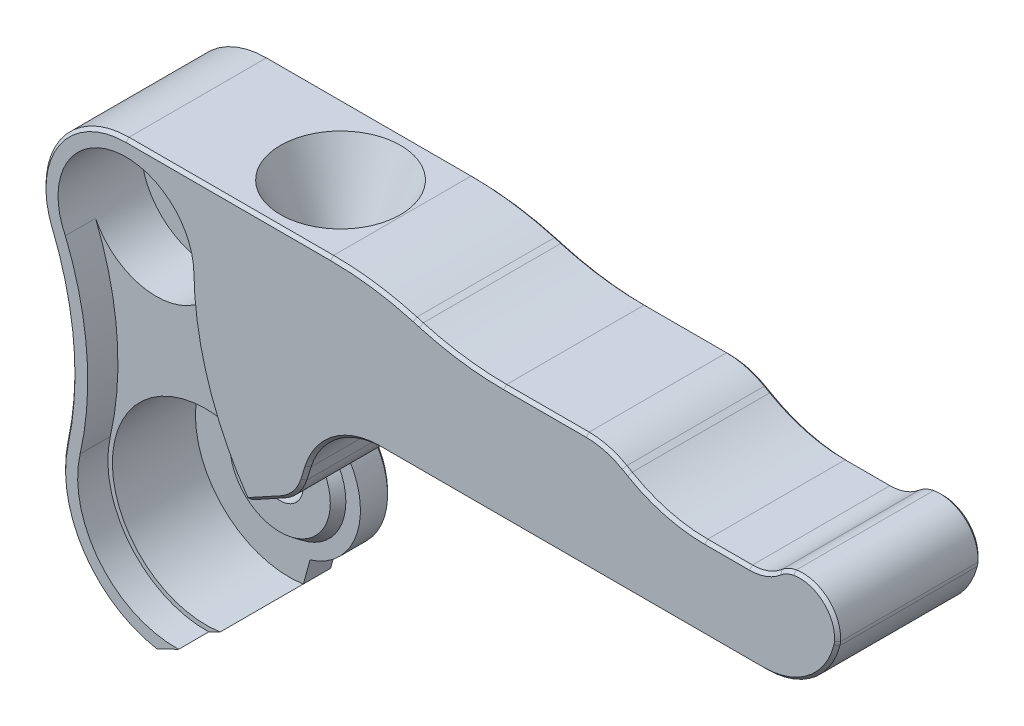
SolidWorks part; units mm, degrees
ref_plane "前视基准面" through (0, 0, 0) normal (0, 0, 1) x (1, 0, 0)
ref_plane "上视基准面" through (0, 0, 0) normal (0, 1, 0) x (1, 0, 0)
ref_plane "右视基准面" through (0, 0, 0) normal (1, 0, 0) x (0, 0, -1)
ref_plane "基准面4" through (0, 0, 14.66) normal (0, 0, 1) x (1, 0, 0)
sketch "草图1" plane through (0, 0, 14.66) normal (0, 0, 1) x (1, 0, 0)
  line L0 (10.0139, 11.6407) -> (26.6958, 11.6407)
  line L2 (-13.7752, -7.3412) -> (-11.2882, -6.1227)
  line L3 (-11.2882, -6.1227) -> (-10.8536, -4.519)
  line L4 (0, 0) -> (50000, 0) construction
  line L5 (-15.5381, 21.0307) -> (-1.986, 21.0307)
  line L6 (-8.9914, 3.4337) -> (-5.1856, 5.5218)
  line L7 (0, 0) -> (0, 50000) construction
  line L8 (-37.0818, 21.1307) -> (32.8827, 21.1307) construction
  line L9 (-21.0381, 33.3889) -> (-21.0381, -18.7776) construction
  line L10 (3.5318, 20.2545) -> (3.954, 20.1333)
  line L12 (9.4717, 19.3571) -> (14.9362, 19.3571)
  line L13 (17.436, 18.6873) -> (17.7909, 18.4824)
  line L14 (22.7906, 17.1429) -> (25.7538, 17.1429)
  line L17 (-3.7672, 7.2509) -> (-3.4865, 8.1424)
  line L18 (1.2827, 11.6407) -> (10.0139, 11.6407)
  arc A0 (-10.8536, -4.519) -> (-8.9914, 3.4337) centre (-12.24, 0) ccw
  arc A1 (-1.986, 21.0307) -> (3.5318, 20.2545) centre (-1.986, 1.0307) cw
  arc A2 (3.954, 20.1333) -> (9.4717, 19.3571) centre (9.4717, 39.3571) ccw
  arc A3 (17.7909, 18.4824) -> (22.7906, 17.1429) centre (22.7906, 27.1429) ccw
  arc A4 (-15.5381, 21.0307) -> (-20.6238, 13.4363) centre (-15.5381, 15.5307) ccw
  arc A5 (-20.6238, 13.4363) -> (-19.5701, 1.5874) centre (-39.117, 5.8205) cw
  arc A6 (-19.5701, 1.5874) -> (-13.7752, -7.3412) centre (-12.24, 0) ccw
  arc A7 (-3.4865, 8.1424) -> (1.2827, 11.6407) centre (1.2827, 6.6407) cw
  arc A8 (26.6958, 11.6407) -> (31.5407, 15.4052) centre (26.6958, 16.6407) ccw
  arc A9 (14.9362, 19.3571) -> (17.436, 18.6873) centre (14.9362, 14.3571) cw
  arc A10 (-5.1856, 5.5218) -> (-3.7672, 7.2509) centre (-6.6287, 8.1519) ccw
  arc A11 (25.7538, 17.1429) -> (27.7036, 17.8629) centre (25.7538, 20.1429) ccw
  arc A12 (28.6527, 18.3119) -> (31.5829, 15.6621) centre (29.091, 15.8516) cw
  arc A13 (28.6527, 18.3119) -> (27.7036, 17.8629) centre (29.0035, 16.3429) ccw
  arc A14 (31.5829, 15.6621) -> (31.5407, 15.4052) centre (30.0872, 15.7758) cw
  dimension "D2" = 20
  dimension "D6" = 5.5
  dimension "D9" = 4.7269
  dimension "D10" = 7.5
  dimension "D11" = 20
  dimension "D12" = 20
  dimension "D13" = 5
  dimension "D14" = 10
  dimension "D15" = 5
  dimension "D16" = 5
  dimension "D17" = 3
  dimension "D18" = 3
  dimension "D19" = 2
  dimension "D20" = 1.5
  dimension "D3" = 12.24
  dimension "D4" = 15.5381
  dimension "D5" = 15.5307
  dimension "D7" = 5.5
  dimension "D8" = 5.6
extrude "凸台-拉伸1" add sketch "草图1" against normal blind 9.5
sketch "草图2" plane through (0, 0, 14.66) normal (0, 0, 1) x (1, 0, 0)
  line L5 (-1.5033, 0) -> (49998.4967, 0) construction
  line L6 (0, -0.31) -> (0, 49999.69) construction
  arc A0 (-18.5763, 1.4497) -> (-7.0407, 3.9009) centre (-12.24, 0) ccw
  arc A1 (-7.0407, 3.9009) -> (-11.0405, 15.5987) centre (8.9571, 15.9038) cw
  arc A3 (-19.6786, 13.7631) -> (-11.0405, 15.5987) centre (-15.54, 15.53) ccw
  arc A4 (-19.6786, 13.7631) -> (-18.5763, 1.4497) centre (-38.0725, 5.9104) cw
  dimension "D2" = 4.5
  dimension "D5" = 6.5
  dimension "D6" = 20
  dimension "D7" = 20
  dimension "D8" = 15.9038
  dimension "D1" = 12.24
  dimension "D3" = 15.54
  dimension "D4" = 15.53
  dimension "D9" = 8.9571
extrude "切除-拉伸1" cut sketch "草图2" against normal blind 2
ref_plane "基准面5" through (0, 0, 12.16) normal (0, 0, 1) x (1, 0, 0)
sketch "草图7" plane through (0, 0, 12.16) normal (0, 0, 1) x (1, 0, 0)
  line L0 (-11.0933, -6.093) -> (-10.7431, -4.7707)
  line L1 (0, 0) -> (50000, 0) construction
  line L2 (0, 0) -> (0, 50000) construction
  arc A0 (-7.2552, 3.6867) -> (-11.0933, -6.093) centre (-12.24, 0) ccw
  arc A1 (-10.7431, -4.7707) -> (-8.4261, 3.2333) centre (-12.24, 0) ccw
  arc A2 (-8.4261, 3.2333) -> (-7.2552, 3.6867) centre (-4.1891, -5.9687) cw
  dimension "D1" = 6.2
  dimension "D2" = 5
  dimension "D3" = 12.24
extrude "切除-拉伸2" cut sketch "草图7" against normal blind 5 and the other way blind 5
ref_plane "基准面7" through (0, 15.5, 0) normal (0, 1, 0) x (1, 0, 0)
sketch "草图20" plane through (0, 15.5, 0) normal (0, 1, 0) x (1, 0, 0)
  line L0 (-13.84, -5.16) -> (-15.54, -5.16)
  line L1 (-15.54, -5.16) -> (-15.54, -14.66)
  line L2 (-15.54, -14.66) -> (-11.04, -14.66)
  line L3 (-11.04, -14.66) -> (-11.04, -9.16)
  line L4 (-11.04, -9.16) -> (-13.84, -9.16)
  line L5 (-13.84, -9.16) -> (-13.84, -5.16)
  line L6 (-15.54, -5.16) -> (-15.54, -14.66) construction
  dimension "D1" = 15.54
  dimension "D2" = 1.7
  dimension "D3" = 4.5
  dimension "D4" = 5.5
revolve "切除-旋转1" cut sketch "草图20" angle 360 about L1 reverse direction yes
ref_plane "基准面11" through (0, 0, 9.91) normal (0, 0, 1) x (1, 0, 0)
sketch "草图28" plane through (0, 0, 9.91) normal (0, 0, -1) x (-1, 0, 0)
  line L0 (-15.0459, 9.1407) -> (-14.15, 9.1407)
  line L1 (-14.15, 9.1407) -> (-14.15, 11.6407)
  line L2 (-14.15, 11.6407) -> (-18.65, 11.6407)
  line L3 (-14.15, 7.6293) -> (-14.15, 10.1306) construction
  line L4 (0, 0) -> (-50000, 0) construction
  line L5 (0, 0) -> (0, 50000) construction
  line L7 (-1.2827, 11.6407) -> (-26.6958, 11.6407) construction
  line L8 (-18.65, 11.6407) -> (-18.0215, 11.424)
  arc A0 (-17.4041, 10.8106) -> (-15.0459, 9.1407) centre (-15.0459, 11.6407) ccw
  arc A1 (-18.0215, 11.424) -> (-17.4041, 10.8106) centre (-18.3474, 10.4786) cw
  dimension "D3" = 2.5
  dimension "D2" = 1
  dimension "D1" = 2.5
  dimension "D4" = 0.8959
  dimension "D5" = 0.8959
  dimension "D6" = 4.5
revolve "旋转1" add sketch "草图28" angle 360 about L1 reverse direction yes
sketch "草图31" plane through (0, 0, 0) normal (0, 1, 0) x (1, 0, 0)
  line L0 (-8.4777, -7.16) -> (-12.24, -7.16)
  line L1 (-12.24, -7.16) -> (-12.24, -7.7517)
  line L4 (-10.2, -7.7517) -> (-8.9163, -7.7517)
  line L5 (-8.9163, -7.7517) -> (-8.4777, -7.16)
  line L6 (-12.24, -7.16) -> (-12.24, -13.46) construction
  line L7 (0, 0) -> (50000, 0) construction
  line L8 (0, 0) -> (0, 50000) construction
  line L9 (-1.986, -5.16) -> (-15.5381, -5.16) construction
  line L10 (-10.2, -7.7517) -> (-12.24, -7.7517)
  dimension "D2" = 12.24
  dimension "D4" = 2
revolve "旋转2" add sketch "草图31" angle 360 about L1 reverse direction yes
ref_axis "基准轴1" through (-5.6405, -54.979, 9.82) along (-0.0057, 1, 0)
ref_plane "基准面10" through (-5.9518, -0.0337, 0) normal (1, 0.0057, 0) x (0, 0, -1)
sketch "草图34" plane through (-5.9521, 0.0158, 0) normal (1, 0.0057, 0) x (0, 0, -1)
  line L0 (-5.16, 11.4396) -> (-5.16, 15.1767) construction
  line L1 (-9.91, 21.0689) -> (-9.91, 4.0689)
  line L2 (-5.16, 21.0689) -> (-14.66, 21.0689) construction
  line L3 (-9.91, 4.0689) -> (-8.61, 4.0689)
  line L4 (-9.91, 110) -> (-9.91, -10) construction
  line L5 (-9.91, 21.0689) -> (-5.91, 21.0689)
  line L6 (-5.91, 21.0689) -> (-8.11, 16.0689)
  line L7 (-8.11, 16.0689) -> (-8.61, 4.0689)
  dimension "D1" = 4.75
  dimension "D2" = 17
  dimension "D3" = 1.3
  dimension "D4" = 5
  dimension "D5" = 1.8
  dimension "D6" = 4
revolve "切除-旋转2" cut sketch "草图34" angle 360 about L4
chamfer "倒角3" distance 0.2 angle 45 25 edges at (31.5674, 15.5327, 5.16) (29.7635, 12.6924, 5.16) (30.7673, 17.7051, 5.16) (28.1482, 18.1508, 5.16) (26.7931, 17.3286, 5.16) (24.2722, 17.1429, 5.16) (20.2026, 17.4836, 5.16) (17.6135, 18.5849, 5.16) (16.2302, 19.1868, 5.16) (12.204, 19.3571, 5.16) (6.6857, 19.5521, 5.16) (3.7429, 20.1939, 5.16) (0.8001, 20.8357, 5.16) (-8.7621, 21.0307, 5.16) (-20.1081, 18.591, 5.16) (-19.1956, 7.592, 5.16) (-18.5311, -4.0831, 5.16) (-12.5317, -6.732, 5.16) (-11.0709, -5.3209, 5.16) (-7.6376, -1.0777, 5.16) (-7.0885, 4.4777, 5.16) (-4.3092, 6.2492, 5.16) (-3.6268, 7.6966, 5.16) (-1.6746, 10.6723, 5.16) (13.9892, 11.6407, 5.16)
chamfer "倒角4" distance 0.2 angle 45 1 edges at (-13.84, 15.5, 5.16)
chamfer "倒角5" distance 0.2 angle 45 22 edges at (-18.5311, -4.0831, 14.66) (-19.1956, 7.592, 14.66) (-20.1081, 18.591, 14.66) (-8.7621, 21.0307, 14.66) (0.8001, 20.8357, 14.66) (3.7429, 20.1939, 14.66) (6.6857, 19.5521, 14.66) (12.204, 19.3571, 14.66) (16.2302, 19.1868, 14.66) (17.6135, 18.5849, 14.66) (20.2026, 17.4836, 14.66) (24.2722, 17.1429, 14.66) (26.7931, 17.3286, 14.66) (28.1482, 18.1508, 14.66) (30.7673, 17.7051, 14.66) (31.5674, 15.5327, 14.66) (29.7635, 12.6924, 14.66) (13.9892, 11.6407, 14.66) (-1.6746, 10.6723, 14.66) (-3.6268, 7.6966, 14.66) (-4.3092, 6.2492, 14.66) (-6.2703, 4.9267, 14.66)
sketch "草图35" plane through (0, 0, 7.7517) normal (0, 0, 1) x (1, 0, 0)
  circle A0 centre (-12.24, 0) radius 1.52
  dimension "D1" = 3.04
extrude "切除-拉伸3" cut sketch "草图35" against normal blind 2
ref_axis "基准轴2" through (-6.1623, 37.1138, 9.91) along (0.0057, -1, 0)
